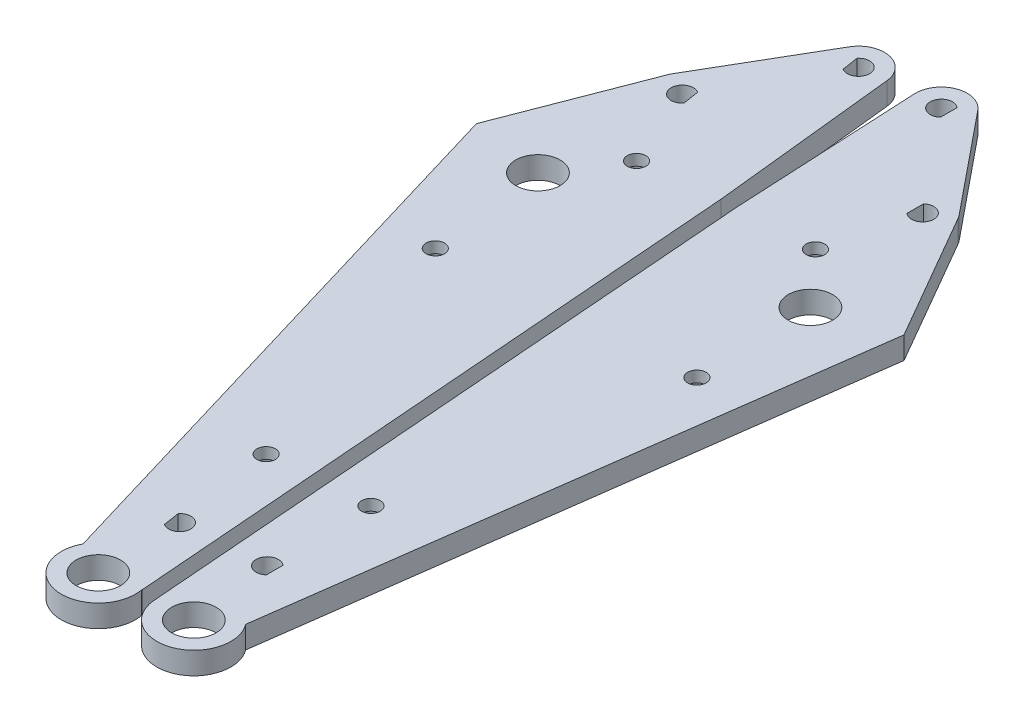
SolidWorks part; units mm, degrees
note: The reader was unsure of these and kept them because the rebuilt part matched: shared geometry of "草图4<3>", "草图4<4>", "草图6<3>".
ref_plane "前视基准面" through (0, 0, 0) normal (0, 0, 1) x (1, 0, 0)
ref_plane "上视基准面" through (0, 0, 0) normal (0, 1, 0) x (1, 0, 0)
ref_plane "右视基准面" through (0, 0, 0) normal (1, 0, 0) x (0, 0, -1)
other "Configuration Table"
sketch "草图2" plane through (0, 0, 0) normal (0, 1, 0) x (1, 0, 0)
  line L8 (-15.2382, -15.3821) -> (-8, 0)
  line L9 (-8, 0) -> (0, 0)
  line L10 (0, 0) -> (10.9793, -19.0167)
  line L11 (10.9793, -19.0167) -> (1.4123, -100.4567) construction
  line L12 (1.4123, -100.4567) -> (-8.6437, -100.1259)
  line L13 (-8.6437, -100.1259) -> (-15.2382, -15.3821)
  line L14 (-15.2382, -15.3821) -> (1.4511, -22.125)
  line L15 (1.35, -100.8754) -> (10.9793, -19.0167)
  line L16 (-3.0207, -2.382) -> (-3.0207, -4.618)
  circle A9 centre (1.4511, -22.125) radius 3
  circle A10 centre (-3.6157, -100.2913) radius 3
  circle A11 centre (-3.6157, -100.2913) radius 5
  circle A12 centre (-2.0207, -3.5) radius 1.5
  circle A13 centre (-2.0207, -3.5) radius 3.5
  dimension "D10" = 18
  dimension "D12" = 6
  dimension "D14" = 3
  dimension "D15" = 2
  dimension "D13" = 6
  dimension "D6" = 2
  dimension "D1" = 8
  dimension "D2" = 13
  dimension "D3" = 17
  dimension "D4" = 85
  dimension "D5" = 82
  dimension "D7" = 120
  dimension "D8" = 115.2
  dimension "D9" = 143.3
  dimension "D11" = 86.8
  dimension "D16" = 1
extrude "凸台-拉伸1" add sketch "草图2" along normal blind 3
sketch "草图3" plane through (0, 0, 0) normal (0, -1, 0) x (1, 0, 0)
  line L5 (-12, -8.882) -> (-12, -11.118)
  circle A0 centre (-13, -10) radius 1.5
  circle A1 centre (-13, -10) radius 3.5
  dimension "D1" = 3
  dimension "D2" = 2
  dimension "D3" = 10
  dimension "D4" = 13
  dimension "D7" = 1
extrude "凸台-拉伸2" add sketch "草图3" against normal up to surface (3 mm away)
sketch "草图4" plane through (0, 0, 0) normal (0, -1, 0) x (1, 0, 0)
  line L0 (-3.9163, 90.0371) -> (-4.0898, 87.8078)
  line L1 (-8.6437, 100.1259) -> (-15.2382, 15.3821) construction
  line L2 (0.3843, 97.2913) -> (10.9793, 19.0167)
  line L3 (1.3994, 100.4562) -> (10.9793, 19.0167) construction
  line L4 (1.0104, 1.75) -> (10.9793, 19.0167) construction
  circle A0 centre (-5, 89) radius 1.5
  circle A1 centre (-5, 89) radius 3.5
  circle A2 centre (-3.6157, 100.2913) radius 5
  circle A3 centre (-3.6157, 100.2913) radius 3 construction
  arc A4 (1.3816, 100.4556) -> (-8.613, 100.1269) centre (-3.6157, 100.2913) ccw construction
  line M11 (1.3994, 100.4562) -> (1.3816, 100.4556)
  line M14 (-8.6437, 100.1259) -> (-15.2382, 15.3821)
  line M25 (10.9793, 19.0167) -> (1.3994, 100.4562)
  dimension "D1" = 3
  dimension "D2" = 2
  dimension "D3" = 89
  dimension "D4" = 5
  dimension "D5" = 1
  dimension "D6" = 4
extrude "凸台-拉伸3" add sketch "草图4" against normal up to surface (3 mm away) contours A1 up to face at (-3.6157, 3, 103.2913)
extrude "切除-拉伸1" cut sketch "草图4<3>" against normal through all contours A0 L0 M14 | A0 M14
sketch "草图4<3>" plane through (0, 0, 0) normal (0, -1, 0) x (1, 0, 0) same geometry as "草图4"
extrude "切除-拉伸2" cut sketch "草图4<4>" against normal through all contours A2 L2 M25 M11
sketch "草图4<4>" plane through (0, 0, 0) normal (0, -1, 0) x (1, 0, 0) same geometry as "草图4"
sketch "草图5" plane through (0, 0, 0) normal (0, -1, 0) x (1, 0, 0)
  line L0 (0.6946, 1.2917) -> (-10.2846, -12.2083)
  line L1 (-16.4957, -9.8256) -> (-15.2382, 15.3821)
  line L2 (-15.2382, 15.3821) -> (-8, 0) construction
  line L5 (-8.6437, 100.1259) -> (-15.2382, 15.3821) construction
  line L6 (-15.2382, 15.3821) -> (-8, 0)
  line L7 (-8, 0) -> (-2.0207, 0) construction
  line L8 (-8, 0) -> (0.6946, 1.2917)
  line L10 (-4, 87.882) -> (-4, 90.118)
  arc A0 (-2.0207, 0) -> (1.0104, 1.75) centre (-2.0207, 3.5) ccw construction
  circle A1 centre (-13, -10) radius 3.5 construction
  circle A2 centre (-13, -10) radius 3.5
  circle A3 centre (-5, 89) radius 1.5
  circle A4 centre (-5, 89) radius 1.5 construction
  circle M8 centre (-5, 89) radius 1.5
  line M13 (-15.2382, 15.3821) -> (-8, 0)
  line M14 (-8, 0) -> (-2.0207, 0)
  arc M15 (-2.0207, 0) -> (1.0104, 1.75) centre (-2.0207, 3.5) ccw
  dimension "D1" = 1
extrude "凸台-拉伸4" add sketch "草图5" against normal up to surface (3 mm away) contours A2 L0 L1 M15 M14 M13 | L10 M8
sketch "草图6" plane through (0, 0, 0) normal (0, -1, 0) x (1, 0, 0)
  circle A0 centre (-5, 15) radius 2
  circle A1 centre (-5, 15) radius 1.25
  circle A2 centre (2, 38) radius 2
  circle A3 centre (2, 38) radius 1.25
  circle A4 centre (-5, 75) radius 2
  circle A5 centre (-5, 75) radius 1.25
  dimension "D3" = 4
  dimension "D4" = 2.5
  dimension "D1" = 15
  dimension "D2" = 5
  dimension "D5" = 38
  dimension "D6" = 2
  dimension "D7" = 75
  dimension "D8" = 5
extrude "切除-拉伸3" cut sketch "草图6" against normal through all contours A1 | A3 | A5
extrude "切除-拉伸4" cut sketch "草图6<3>" against normal blind 1.5
sketch "草图6<3>" plane through (0, 0, 0) normal (0, -1, 0) x (1, 0, 0) same geometry as "草图6"
ref_plane "基准面1" through (-17.3333, 0, 1.3488) normal (-0.997, 0, 0.0776) x (0.0776, 0, 0.997)
mirror "镜向2" about plane through (-17.3333, 0, 1.3488) normal (-0.997, 0, 0.0776) of bodies 129
